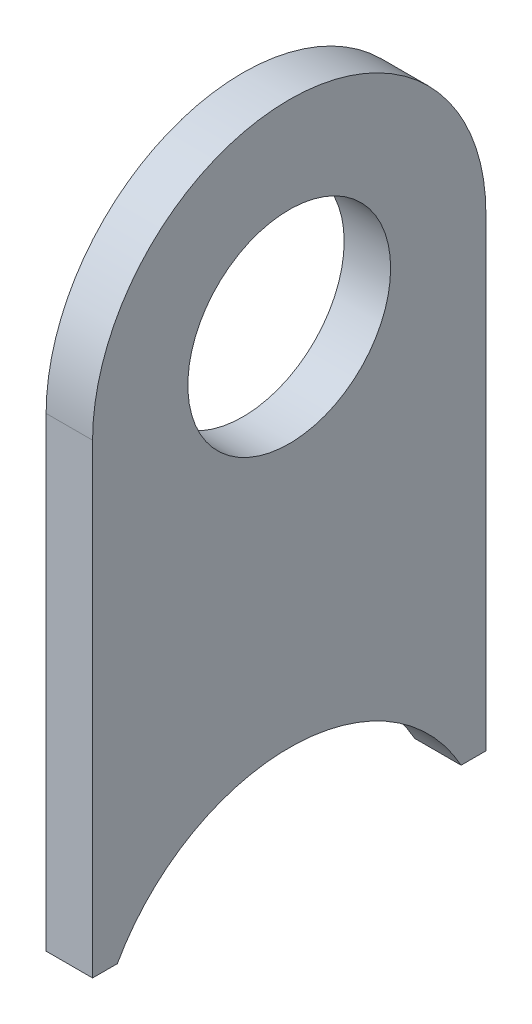
SolidWorks part; units mm, degrees
ref_plane "Front Plane" through (0, 0, 0) normal (0, 0, 1) x (1, 0, 0)
ref_plane "Top Plane" through (0, 0, 0) normal (0, 1, 0) x (1, 0, 0)
ref_plane "Right Plane" through (0, 0, 0) normal (1, 0, 0) x (0, 0, -1)
sketch "Sketch1" plane through (0, 0, 0) normal (1, 0, 0) x (0, 0, -1)
  line L0 (0, 12.7) -> (-24.9297, 12.7) construction
  line L1 (0, 29.7) -> (-24.9297, 29.7) construction
  line L2 (-12.7, 36.2481) -> (-12.7, 6.1709)
  line L3 (12.7, 36.2481) -> (12.7, 6.1709)
  line L4 (-11.1, 6.1709) -> (-12.7, 6.1709)
  line L5 (11.1, 6.1709) -> (12.7, 6.1709)
  circle A0 centre (0, 0) radius 12.7 construction
  circle A1 centre (0, 36.2481) radius 6.5481
  arc A2 (-12.7, 36.2481) -> (12.7, 36.2481) centre (0, 36.2481) cw
  arc A3 (-11.1, 6.1709) -> (11.1, 6.1709) centre (0, 0) cw
  dimension "D1" = 25.4
  dimension "D2" = 13.0962
  dimension "D3" = 17
  dimension "D5" = 1.6
extrude "Boss-Extrude1" add sketch "Sketch1" along normal blind 1.5 and the other way blind 1.5
